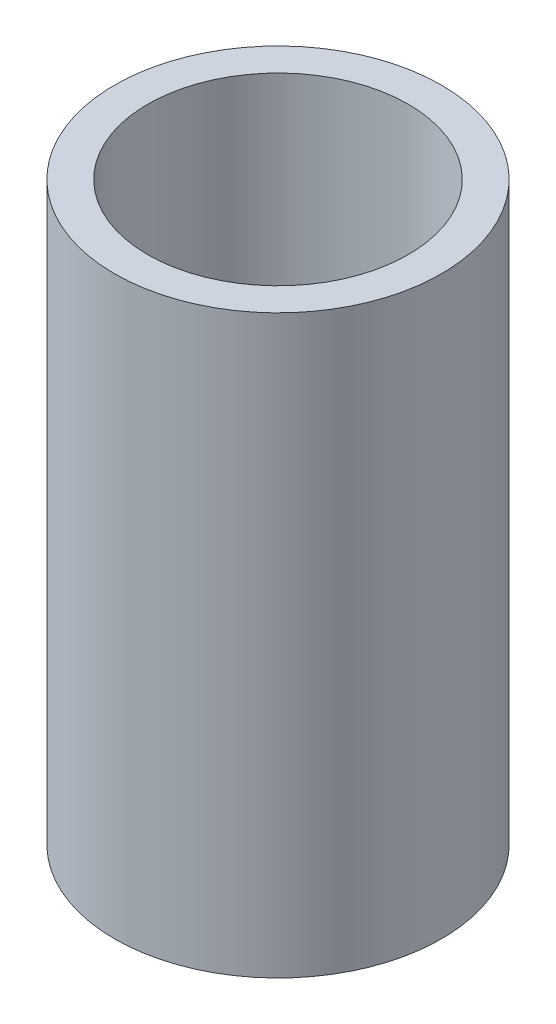
SolidWorks part; units mm, degrees
ref_plane "Front Plane" through (0, 0, 0) normal (0, 0, 1) x (1, 0, 0)
ref_plane "Top Plane" through (0, 0, 0) normal (0, 1, 0) x (1, 0, 0)
ref_plane "Right Plane" through (0, 0, 0) normal (1, 0, 0) x (0, 0, -1)
sketch "Sketch1" plane through (0, 0, 0) normal (0, 1, 0) x (1, 0, 0)
  circle A0 centre (0, 0) radius 20
  dimension "SLEEVE_OD" = 40
extrude "Boss-Extrude1" add sketch "Sketch1" along normal blind 70.4903
sketch "Sketch2" plane through (0, 0, 0) normal (0, 1, 0) x (1, 0, 0)
  circle A0 centre (0, 0) radius 15.9476
  dimension "BORE_D" = 31.8952
extrude "Cut-Extrude1" cut sketch "Sketch2" along normal through all
chamfer "Chamfer1" distance 3.89 angle 62.904 rebuild error yes
